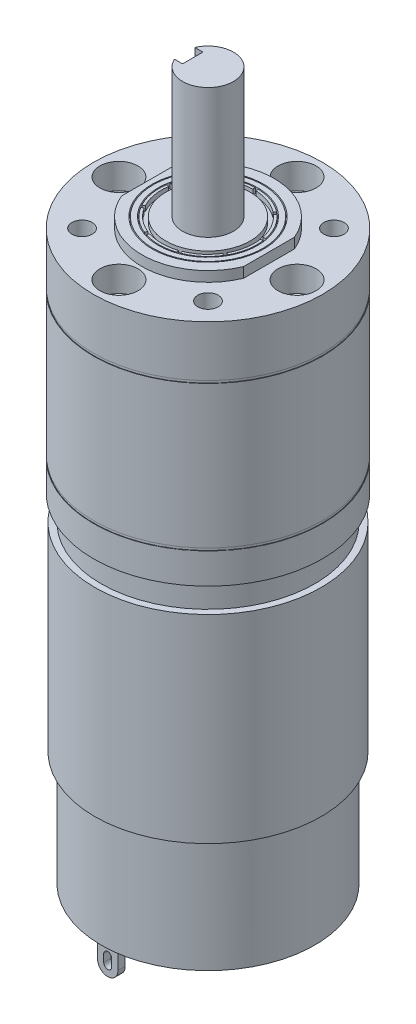
SolidWorks part; units mm, degrees
material "Stainless Steel (ferritic)"
ref_plane "Front Plane" through (0, 0, 0) normal (0, 0, 1) x (1, 0, 0)
ref_plane "Top Plane" through (0, 0, 0) normal (0, 1, 0) x (1, 0, 0)
ref_plane "Right Plane" through (0, 0, 0) normal (1, 0, 0) x (0, 0, -1)
sketch "Sketch1" plane through (0, 0, 0) normal (0, 1, 0) x (1, 0, 0)
  circle A0 centre (0, 0) radius 21
  dimension "D1" = 42
extrude "Boss-Extrude1" add sketch "Sketch1" along normal blind 66.5
fillet "Fillet1" radius 1 1 edges at (0, 66.5, 21) conic rho 0.5
sketch "Sketch2" plane through (0, 66.5, 0) normal (0, 1, 0) x (1, 0, 0)
  circle A0 centre (0, 0) radius 22.5
  dimension "D1" = 45
extrude "Boss-Extrude2" add sketch "Sketch2" along normal blind 45
sketch "Sketch3" plane through (0, 111.5, 0) normal (0, 1, 0) x (1, 0, 0)
  circle A0 centre (0, 0) radius 13
  dimension "D1" = 26
extrude "Boss-Extrude3" add sketch "Sketch3" along normal blind 2
sketch "Sketch4" plane through (0, 111.5, 0) normal (0, 1, 0) x (1, 0, 0)
  circle A0 centre (0, 0) radius 5
extrude "Boss-Extrude4" add sketch "Sketch4" along normal blind 27.5
ref_plane "Plane1" through (0, 101.5, 0) normal (0, 1, 0) x (1, 0, 0)
sketch "Sketch5" plane through (0, 101.5, 0) normal (0, 1, 0) x (1, 0, 0)
  circle A0 centre (0, 0) radius 22.5
  circle A1 centre (0, 0) radius 22.4
  dimension "D1" = 0.1
extrude "Cut-Extrude1" cut sketch "Sketch5" against normal blind 0.5
ref_plane "Plane2" through (0, 72.5, 0) normal (0, -1, 0) x (-1, 0, 0)
sketch "Sketch6" plane through (0, 72.5, 0) normal (0, -1, 0) x (-1, 0, 0)
  circle A0 centre (0, 0) radius 22.5
  circle A1 centre (0, 0) radius 22.4
  dimension "D1" = 0.1
extrude "Cut-Extrude6" cut sketch "Sketch6" against normal blind 0.5
ref_plane "Plane3" through (0, 100.5, 0) normal (0, 1, 0) x (1, 0, 0)
ref_axis "Axis1" through (0, 101, 0) along (0, -1, 0)
ref_plane "Plane4" through (0, 61.5, 0) normal (0, -1, 0) x (-1, 0, 0)
sketch "Sketch12" plane through (0, 61.5, 0) normal (0, -1, 0) x (-1, 0, 0)
  line L2 (0.75, 22.1337) -> (0.75, 21.0829)
  line L4 (-0.75, 22.1337) -> (-0.75, 21.0829)
  arc A0 (-0.8538, 22.2336) -> (0.8538, 22.2336) centre (0, 0) ccw
  arc A1 (-0.846, 20.983) -> (0.846, 20.983) centre (0, 0) ccw
  arc A2 (0.75, 22.1337) -> (0.8538, 22.2336) centre (0.85, 22.1337) cw
  arc A3 (0.846, 20.983) -> (0.75, 21.0829) centre (0.85, 21.0829) cw
  arc A4 (-0.75, 21.0829) -> (-0.846, 20.983) centre (-0.85, 21.0829) cw
  arc A5 (-0.8538, 22.2336) -> (-0.75, 22.1337) centre (-0.85, 22.1337) cw
  point P4 (0, 21)
  point P5 (-0.75, 21)
  point P6 (0.75, 21)
  dimension "D1" = 44.5
  dimension "D2" = 0.75
  dimension "D4" = 0.1
  dimension "D3" = 0.75
extrude "Boss-Extrude5" add sketch "Sketch12" along normal blind 39
sketch "Sketch13" plane through (0, 0, 0) normal (0, -1, 0) x (1, 0, 0)
  circle A1 centre (0, 0) radius 20.5
extrude "Cut-Extrude10" cut sketch "Sketch13" against normal blind 1
sketch "Sketch14" plane through (0, 111.5, 0) normal (0, 1, 0) x (1, 0, 0)
  line L0 (-15, 16.5) -> (-15, -16.5)
  line L1 (12, 13.5) -> (-12, 13.5)
  line L2 (12, 13.5) -> (12, -13.5)
  line L3 (12, -13.5) -> (-12, -13.5)
  line L4 (-12, 13.5) -> (-12, -13.5)
  line L5 (12, 13.5) -> (-12, -13.5) construction
  line L6 (12, -13.5) -> (-12, 13.5) construction
  line L7 (15, -16.5) -> (-15, -16.5)
  line L8 (15, 16.5) -> (15, -16.5)
  line L9 (15, 16.5) -> (-15, 16.5)
  point P0 (0, 0)
  dimension "D1" = 24
  dimension "D2" = 27
  dimension "D3" = 3
extrude "Cut-Extrude11" cut sketch "Sketch14" along normal blind 6
sketch "Sketch15" plane through (0, 113.5, 0) normal (0, 1, 0) x (1, 0, 0)
  circle A0 centre (0, 0) radius 10.8
  circle A1 centre (0, 0) radius 11
  dimension "D1" = 0.2
extrude "Cut-Extrude12" cut sketch "Sketch15" against normal blind 1
sketch "Sketch16" plane through (0, 113.5, 0) normal (0, 1, 0) x (1, 0, 0)
  circle A0 centre (0, 0) radius 9.6
  circle A1 centre (0, 0) radius 9.8
  dimension "D1" = 0.2
extrude "Cut-Extrude13" cut sketch "Sketch16" against normal blind 1
sketch "Sketch17" plane through (0, 113.5, 0) normal (0, 1, 0) x (1, 0, 0)
  circle A0 centre (0, 0) radius 8.3
  circle A1 centre (0, 0) radius 9.1
  dimension "D1" = 0.8
extrude "Cut-Extrude14" cut sketch "Sketch17" against normal blind 1
sketch "Sketch18" plane through (0, 113.5, 0) normal (0, 1, 0) x (1, 0, 0)
  line L1 (-0.3, 9.5953) -> (-0.3, 9.0951)
  line L2 (0.3, 9.5953) -> (0.3, 9.0951)
  circle A0 centre (0, 0) radius 0.3
  arc A1 (0.3, 9.0951) -> (-0.3, 9.0951) centre (0, 0) ccw
  arc A2 (0.3, 9.5953) -> (-0.3, 9.5953) centre (0, 0) ccw
  point P0 (0, 10.2242)
  point P1 (0, 8.7324)
  point P3 (-0.3, 10.2242)
  point P4 (-0.3, 8.7324)
  point P5 (0.3, 10.2242)
  point P6 (0.3, 8.7324)
extrude "Cut-Extrude15" cut sketch "Sketch18" against normal blind 1
pattern_circular "CirPattern3" count 9 every 40 about axis through (0, 101, 0) along (0, -1, 0) of "Cut-Extrude15"
sketch "Sketch19" plane through (0, 139, 0) normal (0, 1, 0) x (1, 0, 0)
  line L1 (-5, 2) -> (-3, 2)
  line L2 (-5, 2) -> (-5, -2)
  line L3 (-5, -2) -> (-3, -2)
  line L4 (-3, 2) -> (-3, -2)
  circle A0 centre (0, 0) radius 5 construction
  point P0 (-5, 0)
  point P1 (-3, 0)
  point P4 (-3, 2)
  point P5 (-3, -2)
  dimension "D1" = 2
  dimension "D2" = 2
  dimension "D3" = 2
extrude "Cut-Extrude16" cut sketch "Sketch19" against normal blind 18
sketch "Sketch20" plane through (-3, 0, 0) normal (-1, 0, 0) x (0, 0, 1)
  line L0 (2, 121) -> (-2, 121) construction
  circle A0 centre (0, 121) radius 2
extrude "Cut-Extrude17" cut sketch "Sketch20" along normal blind 3
sketch "Sketch21" plane through (0, 111.5, 0) normal (0, 1, 0) x (1, 0, 0)
  circle A0 centre (0, 17.5) radius 2
  point P0 (0, 17.5)
  dimension "D1" = 17.5
extrude "Cut-Extrude18" cut sketch "Sketch21" against normal blind 20
pattern_circular "CirPattern4" count 8 every 45 about axis through (0, 101, 0) along (0, -1, 0) of "Cut-Extrude18"
sketch "Sketch22" plane through (0, 111.5, 0) normal (0, 1, 0) x (1, 0, 0)
  circle A0 centre (0, 17.5) radius 3.75
  dimension "D1" = 7.5
extrude "Cut-Extrude19" cut sketch "Sketch22" against normal blind 5
pattern_circular "CirPattern5" count 4 every 90 about axis through (0, 101, 0) along (0, -1, 0) of "Cut-Extrude19"
sketch "Sketch24" plane through (0, 0, 0) normal (0, -1, 0) x (1, 0, 0)
  line L1 (-2, -19.7121) -> (2, -19.7121)
  line L2 (-2, -19.7121) -> (-2, -18.2879)
  line L3 (-2, -18.2879) -> (2, -18.2879)
  line L4 (2, -19.7121) -> (2, -18.2879)
  line L5 (-2, -19.7121) -> (2, -18.2879) construction
  line L6 (-2, -18.2879) -> (2, -19.7121) construction
  line L7 (-2, 18.2879) -> (2, 19.7121) construction
  line L8 (-2, 19.7121) -> (2, 18.2879) construction
  line L9 (2, 19.7121) -> (2, 18.2879)
  line L10 (-2, 18.2879) -> (2, 18.2879)
  line L11 (-2, 19.7121) -> (-2, 18.2879)
  line L12 (-2, 19.7121) -> (2, 19.7121)
  point P0 (0, -19)
  point P1 (0, -19)
  point P13 (0, 19)
  dimension "D1" = 19
  dimension "D2" = 4
  dimension "D3" = 1.4242
extrude "Boss-Extrude6" add sketch "Sketch24" along normal blind 6 and the other way blind 3
sketch "Sketch25" plane through (0, 0, 19.7121) normal (0, 0, 1) x (1, 0, 0)
  line L0 (2, -6) -> (-2, -6) construction
  line L1 (0, -4) -> (0, -2.4967) construction
  line L2 (2, -6) -> (-2, -6)
  line L3 (2, -6) -> (2, -4)
  line L4 (-0.7815, -4) -> (-0.7815, -2.4967)
  line L5 (-2, -6) -> (-2, -4)
  line L6 (0.7815, -4) -> (0.7815, -2.4967)
  arc A0 (-2, -4) -> (2, -4) centre (0, -4) ccw
  arc A1 (-0.7815, -4) -> (0.7815, -4) centre (0, -4) ccw
  arc A2 (0.7815, -2.4967) -> (-0.7815, -2.4967) centre (0, -2.4967) ccw
  point P0 (0, -6)
  point P1 (0, -4)
  point P5 (0, -3.2483)
  line M1 (2, -6) -> (2, 1)
  line M3 (-2, 1) -> (-2, -6)
  line M4 (-2, -6) -> (2, -6)
  dimension "D1" = 2
extrude "Cut-Extrude20" cut sketch "Sketch25" against normal blind 40 contours A0 L2 M1 | A0 M3 M4 | L4 A2 L6 A1 region at (-1.5533, -5.5533, 19.7121) region at (1.5533, -5.5533, 19.7121)
sketch "Sketch26" plane through (0, 1, 0) normal (0, -1, 0) x (1, 0, 0)
  circle A0 centre (0, 0) radius 6
extrude "Boss-Extrude7" add sketch "Sketch26" along normal blind 3
fillet "Fillet2" radius 1 1 edges at (0, -2, -6) conic rho 0.5
sketch "Sketch27" plane through (0, -2, 0) normal (0, -1, 0) x (1, 0, 0)
  circle A0 centre (0, 0) radius 5
extrude "Boss-Extrude8" add sketch "Sketch27" along normal blind 1.5
fillet "Fillet3" radius 1 1 edges at (0, -3.5, -5) conic rho 0.5
sketch "Sketch28" plane through (0, -3.5, 0) normal (0, -1, 0) x (1, 0, 0)
  circle A0 centre (0, 0) radius 1.5
extrude "Boss-Extrude9" add sketch "Sketch28" along normal blind 3.5
fillet "Fillet4" radius 0.5 1 edges at (0, -7, -1.5) conic rho 0.5
